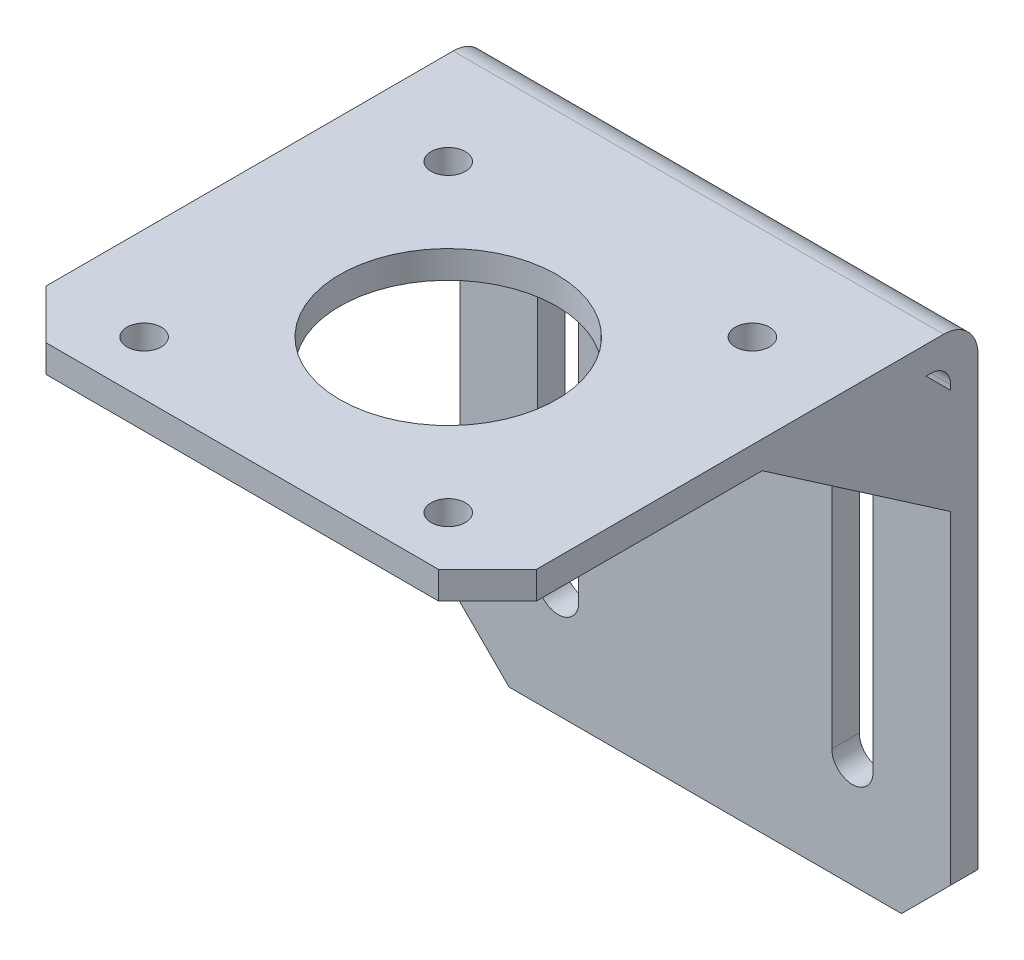
SolidWorks part; units mm, degrees
ref_plane "Front Plane" through (0, 0, 0) normal (0, 0, 1) x (1, 0, 0)
ref_plane "Top Plane" through (0, 0, 0) normal (0, 1, 0) x (1, 0, 0)
ref_plane "Right Plane" through (0, 0, 0) normal (1, 0, 0) x (0, 0, -1)
sketch "Sketch1" plane through (0, 0, 0) normal (1, 0, 0) x (0, 0, -1)
  line L0 (-50, 0) -> (-50, -2.8)
  line L1 (-50, -2.8) -> (-2.8, -2.8)
  line L2 (-2.8, -2.8) -> (-2.8, -54)
  line L3 (-2.8, -54) -> (0, -54)
  line L4 (0, -54) -> (0, 0)
  line L5 (0, 0) -> (-50, 0)
  dimension "D1" = 2.8
  dimension "D2" = 2.8
  dimension "D3" = 50
  dimension "D4" = 54
extrude "Boss-Extrude1" add sketch "Sketch1" along normal blind 25 and the other way blind 25
sketch "Sketch3" plane through (0, 0, 0) normal (0, 1, 0) x (1, 0, 0)
  line L0 (0, 0) -> (0, -50) construction
  line L1 (-25, -50) -> (25, -50) construction
  line L3 (-15.5, -44.5) -> (15.5, -44.5) construction
  line L4 (-15.5, -44.5) -> (-15.5, -13.5) construction
  line L5 (-15.5, -13.5) -> (15.5, -13.5) construction
  line L6 (15.5, -44.5) -> (15.5, -13.5) construction
  line L7 (-15.5, -44.5) -> (15.5, -13.5) construction
  line L8 (-15.5, -13.5) -> (15.5, -44.5) construction
  circle A0 centre (0, -29) radius 11.05
  circle A1 centre (-15.5, -13.5) radius 1.75
  circle A2 centre (15.5, -13.5) radius 1.75
  circle A3 centre (15.5, -44.5) radius 1.75
  circle A4 centre (-15.5, -44.5) radius 1.75
  point P15 (0, -40.05)
  dimension "D2" = 22.1
  dimension "D4" = 3.5
  dimension "D5" = 3.5
  dimension "D6" = 3.5
  dimension "D7" = 3.5
  dimension "D3" = 31
  dimension "D1" = 21
extrude "Cut-Extrude1" cut sketch "Sketch3" against normal through all
sketch "Sketch4" plane through (0, 0, 0) normal (0, 0, -1) x (-1, 0, 0)
  line L0 (-15, 0) -> (-15, -54) construction
  line L1 (25, 0) -> (-25, 0) construction
  line L2 (25, -54) -> (-25, -54) construction
  line L3 (15, 0) -> (15, -54) construction
  line L4 (-15, -43) -> (-15, -13) construction
  line L5 (-17.1, -43) -> (-17.1, -13)
  line L6 (-12.9, -43) -> (-12.9, -13)
  line L7 (15, -43) -> (15, -13) construction
  line L8 (12.9, -43) -> (12.9, -13)
  line L9 (17.1, -43) -> (17.1, -13)
  line L10 (-15, -13) -> (15, -13) construction
  line L11 (-15, -43) -> (15, -43) construction
  arc A0 (-17.1, -43) -> (-12.9, -43) centre (-15, -43) ccw
  arc A1 (-12.9, -13) -> (-17.1, -13) centre (-15, -13) ccw
  arc A2 (12.9, -43) -> (17.1, -43) centre (15, -43) ccw
  arc A3 (17.1, -13) -> (12.9, -13) centre (15, -13) ccw
  point P11 (-15, -28)
  point P18 (15, -28)
  dimension "D1" = 15
  dimension "D2" = 15
  dimension "D3" = 4.2
  dimension "D4" = 4.2
  dimension "D5" = 30
  dimension "D6" = 11
extrude "Cut-Extrude2" cut sketch "Sketch4" against normal through all
chamfer "Chamfer1" distance 5 angle 45 4 edges at (25, -54, 1.4) (-25, -54, 1.4) (-25, -1.4, 50) (25, -1.4, 50)
fillet "Fillet1" radius 2 1 edges at (0, -2.8, 2.8)
fillet "Fillet2" radius 3.5 1 edges at (0, 0, 0)
sketch "Sketch5" plane through (-25, 0, 0) normal (-1, 0, 0) x (0, 0, 1)
  line L0 (2.8, -5.3) -> (5.3, -2.8)
  line L1 (2.8, -4.8) -> (2.8, -49) construction
  line L2 (45, -2.8) -> (4.8, -2.8) construction
  line L3 (5.3, -2.8) -> (22, -2.8)
  line L4 (22, -2.8) -> (2.8, -16)
  line L5 (2.8, -16) -> (2.8, -5.3)
  line L6 (0, -49) -> (0, -3.5) construction
  line L7 (3.5, 0) -> (45, 0) construction
  dimension "D1" = 45
  dimension "D2" = 0.5
  dimension "D3" = 22
  dimension "D4" = 16
extrude "Boss-Extrude2" add sketch "Sketch5" against normal blind 2.5
mirror "Mirror1" about plane through (0, 0, 0) normal (1, 0, 0) of "Boss-Extrude2"
sketch "Sketch6" plane through (0, 0, 2.8) normal (0, 0, 1) x (1, 0, 0)
  line L0 (-20, -54) -> (20, -54) construction
  line L1 (-25, -16) -> (-25, -49) construction
  circle A0 centre (0, -29) radius 3.175
  dimension "D3" = 6.35
  dimension "D1" = 25
  dimension "D2" = 25
extrude "Boss-Extrude3" add sketch "Sketch6" against normal blind 15
equation "\"D5@Sketch3\"=\"D4@Sketch3\""
equation "\"D6@Sketch3\"=\"D4@Sketch3\""
equation "\"D7@Sketch3\"=\"D4@Sketch3\""
equation "\"D4@Sketch4\"=\"D3@Sketch4\""
